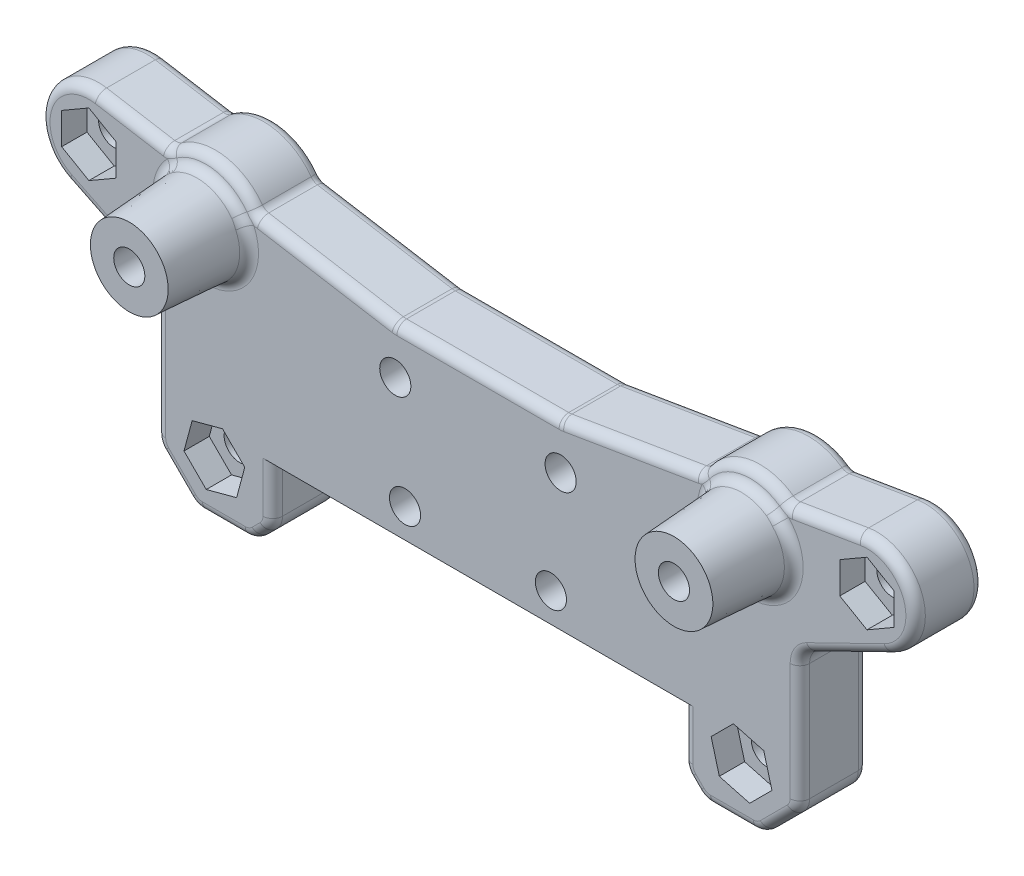
SolidWorks part; units mm, degrees
material "PET"
ref_plane "Plan de face" through (0, 0, 0) normal (0, 0, 1) x (1, 0, 0)
ref_plane "Plan de dessus" through (0, 0, 0) normal (0, 1, 0) x (1, 0, 0)
ref_plane "Plan de droite" through (0, 0, 0) normal (1, 0, 0) x (0, 0, -1)
sketch "Esquisse1" plane through (0, 0, 0) normal (0, 0, 1) x (1, 0, 0)
  line L0 (0, -9.6484) -> (0, 27.7406) construction
  line L1 (21.1, -2.5858) -> (33.1, -2.5858) construction
  line L2 (21.1, 0) -> (21.1, -5.1716)
  line L3 (21.6858, -6.5858) -> (22.5142, -7.4142)
  line L4 (-21.1, -2.5858) -> (-33.1, -2.5858) construction
  line L5 (-39.1727, 23.9312) -> (-31.7479, 22.6855)
  line L6 (-34.2233, 10.6194) -> (-42.1919, 14.506)
  line L7 (-33.1, -3.2216) -> (-33.1, 8.8218)
  line L8 (-29.7358, -7.4142) -> (-32.5142, -4.6358)
  line L9 (-22.9282, 21.2057) -> (-8.6643, 18.8126)
  line L10 (-23.9284, -8) -> (-28.3216, -8)
  line L11 (23.9284, -8) -> (28.3216, -8)
  line L12 (-21.6858, -6.5858) -> (-22.5142, -7.4142)
  line L13 (22.9282, 21.2057) -> (8.6643, 18.8126)
  line L14 (-21.1, 0) -> (-21.1, -5.1716)
  line L18 (29.7358, -7.4142) -> (32.5142, -4.6358)
  line L25 (33.1, -3.2216) -> (33.1, 8.8218)
  line L38 (34.2233, 10.6194) -> (42.1919, 14.506)
  line L133 (39.1727, 23.9312) -> (31.7479, 22.6855)
  line L135 (8.3334, 18.785) -> (-8.3334, 18.785)
  line L804 (-21.1, 0) -> (21.1, 0)
  circle A0 centre (27.1, -2.5858) radius 1.6
  circle A1 centre (8.5, 14) radius 1.6
  circle A2 centre (7.5, 3) radius 1.6
  circle A3 centre (28, 18) radius 1.6
  circle A4 centre (40, 19) radius 1.6
  arc A5 (39.1727, 23.9312) -> (42.1919, 14.506) centre (40, 19) cw
  arc A6 (8.6643, 18.8126) -> (8.3334, 18.785) centre (8.3334, 20.785) cw
  arc A7 (33.1, 8.8218) -> (34.2233, 10.6194) centre (35.1, 8.8218) cw
  arc A8 (33.1, -3.2216) -> (32.5142, -4.6358) centre (31.1, -3.2216) cw
  arc A9 (29.7358, -7.4142) -> (28.3216, -8) centre (28.3216, -6) cw
  arc A10 (23.9284, -8) -> (22.5142, -7.4142) centre (23.9284, -6) cw
  arc A11 (21.1, -5.1716) -> (21.6858, -6.5858) centre (23.1, -5.1716) ccw
  arc A12 (-31.7479, 22.6855) -> (-22.9282, 21.2057) centre (-28, 18) cw
  arc A13 (-21.1, -5.1716) -> (-21.6858, -6.5858) centre (-23.1, -5.1716) cw
  arc A14 (-23.9284, -8) -> (-22.5142, -7.4142) centre (-23.9284, -6) ccw
  arc A15 (-29.7358, -7.4142) -> (-28.3216, -8) centre (-28.3216, -6) ccw
  arc A16 (-33.1, -3.2216) -> (-32.5142, -4.6358) centre (-31.1, -3.2216) ccw
  arc A17 (-33.1, 8.8218) -> (-34.2233, 10.6194) centre (-35.1, 8.8218) ccw
  arc A18 (-8.6643, 18.8126) -> (-8.3334, 18.785) centre (-8.3334, 20.785) ccw
  arc A19 (-39.1727, 23.9312) -> (-42.1919, 14.506) centre (-40, 19) ccw
  circle A20 centre (-40, 19) radius 1.6
  circle A21 centre (-28, 18) radius 1.6
  circle A22 centre (-7.5, 3) radius 1.6
  circle A23 centre (-8.5, 14) radius 1.6
  circle A24 centre (7.5, 3) radius 1.6 construction
  arc A25 (31.7479, 22.6855) -> (22.9282, 21.2057) centre (28, 18) ccw
  circle A26 centre (-27.1, -2.5858) radius 1.6
  point P2 (0, 18.785)
  point P11 (27.1, -2.5858)
  point P12 (21.1, -2.5858)
  point P15 (8.5, 18.785)
  point P23 (29.15, -8)
  point P26 (23.1, -8)
  point P29 (21.1, -6)
  point P31 (-21.1, -6)
  point P32 (0, 18.785)
  point P62 (0, 0)
  point P73 (0, 0)
  point P74 (-23.1, -8)
  point P75 (-29.15, -8)
  point P76 (-8.5, 18.785)
  dimension "D2" = 3.2
  dimension "D6" = 5.0001
  dimension "D16" = 6.05
  dimension "D17" = 2
  dimension "D19" = 6
  dimension "D1" = 42.2
  dimension "D3" = 18.785
  dimension "D4" = 80
  dimension "D5" = 19
  dimension "D7" = 14
  dimension "D8" = 17
  dimension "D9" = 56
  dimension "D10" = 18
  dimension "D11" = 26
  dimension "D12" = 12
  dimension "D13" = 8
  dimension "D14" = 45
  dimension "D15" = 45
  dimension "D18" = 6
extrude "Boss.-Extru.1" add sketch "Esquisse1" along normal blind 7
ref_axis "Axe1" through (28, 18, 7) along (0, 0, -1)
ref_plane "Plan3" through (28, 0, 0) normal (1, 0, 0) x (0, 0, -1)
fillet "Congé1" radius 1 70 edges at (21.1, -2.5858, 0) (21.2522, -5.9369, 0) (22.1, -7, 0) (23.1631, -7.8478, 0) (26.125, -8, 0) (29.087, -7.8478, 0) (31.125, -6.025, 0) (32.9478, -3.987, 0) (33.1, 2.8001, 0) (33.4039, 9.8816, 0) (38.2076, 12.5627, 0) (44.7617, 20.5254, 0) (35.4603, 23.3083, 0) (8.4994, 18.7919, 0) (0, 18.785, 0) (21.1, -2.5858, 7) (21.2522, -5.9369, 7) (22.1, -7, 7) (23.1631, -7.8478, 7) (26.125, -8, 7) (29.087, -7.8478, 7) (31.125, -6.025, 7) (32.9478, -3.987, 7) (33.1, 2.8001, 7) (33.4039, 9.8816, 7) (38.2076, 12.5627, 7) (44.7617, 20.5254, 7) (35.4603, 23.3083, 7) (8.4994, 18.7919, 7) (0, 18.785, 7) (15.7962, 20.0091, 0) (15.7962, 20.0091, 7) (27.0072, 23.9173, 0) (27.0072, 23.9173, 7) (-21.1, -2.5858, 7) (-21.1, -2.5858, 0) (-21.2522, -5.9369, 7) (-21.2522, -5.9369, 0) (-22.1, -7, 7) (-22.1, -7, 0) (-23.1631, -7.8478, 7) (-23.1631, -7.8478, 0) (-26.125, -8, 7) (-26.125, -8, 0) (-29.087, -7.8478, 7) (-29.087, -7.8478, 0) (-31.125, -6.025, 7) (-31.125, -6.025, 0) (-32.9478, -3.987, 7) (-32.9478, -3.987, 0) (-33.1, 2.8001, 7) (-33.1, 2.8001, 0) (-33.4039, 9.8816, 7) (-33.4039, 9.8816, 0) (-38.2076, 12.5627, 7) (-38.2076, 12.5627, 0) (-8.4994, 18.7919, 7) (-8.4994, 18.7919, 0) (-44.7617, 20.5254, 7) (-44.7617, 20.5254, 0) (-15.7962, 20.0091, 7) (-15.7962, 20.0091, 0) (-35.4603, 23.3083, 7) (-35.4603, 23.3083, 0) (-22.9282, 21.2057, 3.5) (-27.0072, 23.9173, 7) (-31.7479, 22.6855, 3.5) (-27.0072, 23.9173, 0) (31.7479, 22.6855, 3.5) (22.9282, 21.2057, 3.5)
sketch "Esquisse5" plane through (28, 0, 0) normal (1, 0, 0) x (0, 0, -1)
  line L0 (-6.8282, 18) -> (-16.9243, 18) construction
  line L1 (-7, 18) -> (0, 18) construction
  line L2 (-14.85, 19.6) -> (-14.85, 22)
  line L3 (-14.85, 22) -> (-7, 22.5)
  line L4 (-7, 23.0001) -> (-7, 15.4047) construction
  line L5 (-7, 22.5) -> (-7, 19.6)
  line L6 (-7, 19.6) -> (-14.85, 19.6)
  dimension "D1" = 8
  dimension "D2" = 9
  dimension "D3" = 7.85
revolve "Révolution1" add sketch "Esquisse5" angle 360 about L0
fillet "Congé2" radius 1 1 edges at (23.5, 18, 7)
sketch "Esquisse3" plane through (0, 0, 7) normal (0, 0, 1) x (1, 0, 0)
  line L0 (29.0287, -6.7071) -> (31.8071, -3.9287) construction
  line L1 (42.8, 17.3834) -> (42.8, 20.6166)
  line L2 (42.8, 20.6166) -> (40, 22.2332)
  line L3 (40, 22.2332) -> (37.2, 20.6166)
  line L4 (37.2, 20.6166) -> (37.2, 17.3834)
  line L5 (37.2, 17.3834) -> (40, 15.7668)
  line L6 (40, 15.7668) -> (42.8, 17.3834)
  line L7 (30.223, -3.4226) -> (29.3862, -0.2996)
  line L8 (29.3862, -0.2996) -> (26.2632, 0.5372)
  line L9 (26.2632, 0.5372) -> (23.977, -1.749)
  line L10 (23.977, -1.749) -> (24.8138, -4.872)
  line L11 (24.8138, -4.872) -> (27.9368, -5.7088)
  line L12 (27.9368, -5.7088) -> (30.223, -3.4226)
  circle A0 centre (40, 19) radius 2.8 construction
  circle A1 centre (27.1, -2.5858) radius 2.8 construction
  dimension "D1" = 5.6
extrude "Enlèv. mat.-Extru.1" cut sketch "Esquisse3" against normal blind 2.6
sketch "Esquisse4" plane through (0, 0, 0) normal (0, 0, -1) x (-1, 0, 0)
  line L0 (-32.3342, 21.7699) -> (-39.3381, 22.9449) construction
  line L1 (-24.8114, 17.465) -> (-25.9424, 20.4939)
  line L2 (-25.9424, 20.4939) -> (-29.131, 21.0289)
  line L3 (-29.131, 21.0289) -> (-31.1886, 18.535)
  line L4 (-31.1886, 18.535) -> (-30.0576, 15.5061)
  line L5 (-30.0576, 15.5061) -> (-26.869, 14.9711)
  line L6 (-26.869, 14.9711) -> (-24.8114, 17.465)
  circle A0 centre (-28, 18) radius 2.8 construction
  circle A1 centre (-40, 19) radius 2.8 construction
extrude "Enlèv. mat.-Extru.2" cut sketch "Esquisse4" against normal blind 2.6
mirror "Symétrie2" about plane through (0, 0, 0) normal (1, 0, 0) of "Congé2", "Révolution1", "Enlèv. mat.-Extru.2", "Enlèv. mat.-Extru.1"
